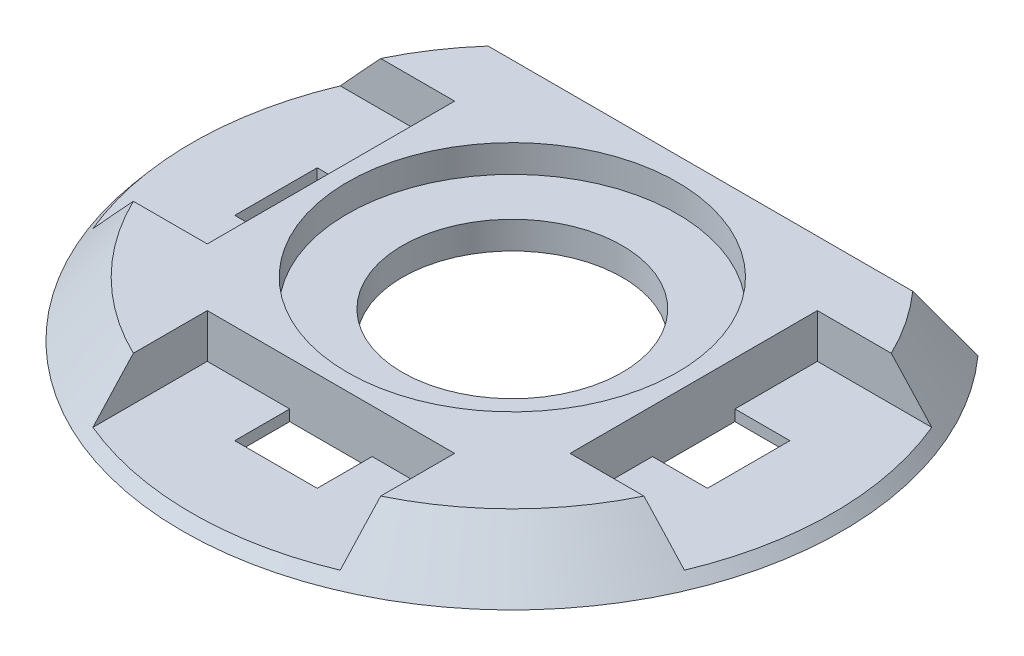
SolidWorks part; units mm, degrees
ref_plane "Front Plane" through (0, 0, 0) normal (0, 0, 1) x (1, 0, 0)
ref_plane "Top Plane" through (0, 0, 0) normal (0, 1, 0) x (1, 0, 0)
ref_plane "Right Plane" through (0, 0, 0) normal (1, 0, 0) x (0, 0, -1)
sketch "Sketch1" plane through (0, 0, 0) normal (0, 1, 0) x (1, 0, 0)
  circle A0 centre (0, 0) radius 60
  dimension "D1" = 120
extrude "Boss-Extrude1" add sketch "Sketch1" along normal blind 10 draft 40
sketch "Sketch2" plane through (0, 10, 0) normal (0, 1, 0) x (1, 0, 0)
  line L1 (-52.8227, 40) -> (49.3012, 40)
  line L2 (-52.8227, 40) -> (-52.8227, 88.4886)
  line L3 (-52.8227, 88.4886) -> (49.3012, 88.4886)
  line L4 (49.3012, 40) -> (49.3012, 88.4886)
  dimension "D1" = 40
extrude "Cut-Extrude1" cut sketch "Sketch2" against normal through all
chamfer "Chamfer1" distance 10 angle 30 1 edges at (0, 10, -40) first distance on face at (3.0275, 5, -40)
sketch "Sketch3" plane through (0, 10, 0) normal (0, 1, 0) x (1, 0, 0)
  circle A0 centre (0, 0) radius 20
extrude "Cut-Extrude2" cut sketch "Sketch3" against normal through all
sketch "Sketch4" plane through (0, 10, 0) normal (0, 1, 0) x (1, 0, 0)
  line L0 (0, 0) -> (33, 0) construction
  line L1 (33, 22.5) -> (68.0356, 22.5)
  line L2 (33, 22.5) -> (33, -22.5)
  line L3 (33, -22.5) -> (68.0356, -22.5)
  line L4 (68.0356, 22.5) -> (68.0356, -22.5)
  dimension "D2" = 33
  dimension "D1" = 45
extrude "Cut-Extrude3" cut sketch "Sketch4" against normal blind 8
sketch "Sketch5" plane through (33, 0, 0) normal (1, 0, 0) x (0, 0, -1)
  line L0 (-18.5, 9.5) -> (18.5, 9.5) construction
  line L1 (0, 0) -> (0, 9.5) construction
  circle A0 centre (-18.5, 9.5) radius 2
  circle A1 centre (18.5, 9.5) radius 2
  dimension "D3" = 4
  dimension "D4" = 4
  dimension "D1" = 37
  dimension "D2" = 9.5
sketch "Sketch6" plane through (0, 2, 0) normal (0, 1, 0) x (1, 0, 0)
  line L0 (33, 22.5) -> (33, -22.5) construction
  line L1 (33, 7.5) -> (43, 7.5)
  line L2 (33, 7.5) -> (33, -7.5)
  line L3 (33, -7.5) -> (43, -7.5)
  line L4 (43, 7.5) -> (43, -7.5)
  line L5 (33, 0) -> (0, 0) construction
  dimension "D1" = 15
  dimension "D2" = 10
extrude "Cut-Extrude5" cut sketch "Sketch6" against normal through all
pattern_circular "CirPattern1" count 3 every 90 about axis through (0, 10, 0) along (0, 1, 0) of "Cut-Extrude3", "Cut-Extrude5" reverse direction yes
sketch "Sketch7" plane through (0, 10, 0) normal (0, 1, 0) x (1, 0, 0)
  circle A0 centre (0, 0) radius 30
extrude "Cut-Extrude6" cut sketch "Sketch7" against normal blind 5
